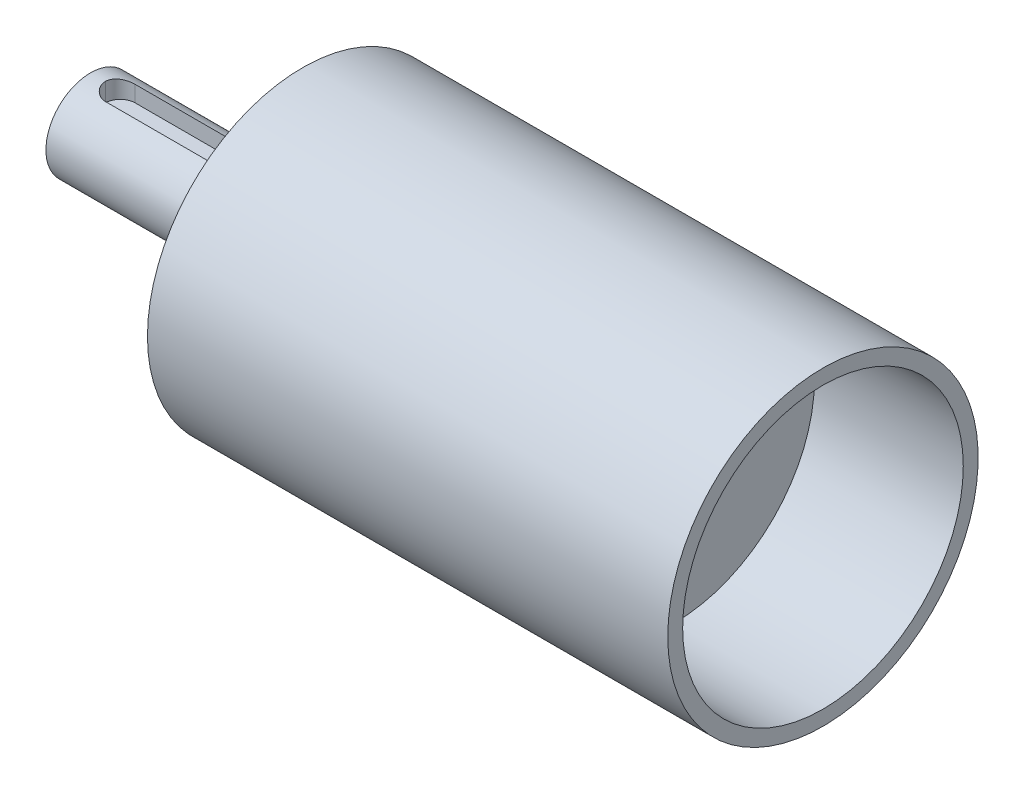
SolidWorks part; units mm, degrees
ref_plane "Front Plane" through (0, 0, 0) normal (0, 0, 1) x (1, 0, 0)
ref_plane "Top Plane" through (0, 0, 0) normal (0, 1, 0) x (1, 0, 0)
ref_plane "Right Plane" through (0, 0, 0) normal (1, 0, 0) x (0, 0, -1)
sketch "Sketch1" plane through (0, 0, 0) normal (1, 0, 0) x (0, 0, -1)
  circle A0 centre (0, 0) radius 5.99
  dimension "D1" = 11.98
extrude "Extrude1" add sketch "Sketch1" along normal blind 25.9
sketch "Sketch2" plane through (25.9, 0, 0) normal (1, 0, 0) x (0, 0, -1)
  circle A0 centre (0, 0) radius 13.985
  dimension "D1" = 27.97
extrude "Extrude2" add sketch "Sketch2" along normal blind 2.6
sketch "Sketch3" plane through (28.5, 0, 0) normal (1, 0, 0) x (0, 0, -1)
  circle A0 centre (0, 0) radius 20.85
  dimension "D1" = 41.7
extrude "Extrude3" add sketch "Sketch3" along normal blind 69.9
sketch "Sketch6" plane through (0, 0, 0) normal (-1, 0, 0) x (0, 0, 1)
  line L0 (0, 5.99) -> (0, 3.49)
  line L1 (-2, 3.49) -> (2, 3.49)
  line L2 (2, 3.49) -> (2, 5.99)
  line L3 (2, 5.99) -> (-2, 5.99)
  line L4 (-2, 5.99) -> (-2, 3.49)
  circle A0 centre (0, 0) radius 5.99 construction
  circle M1 centre (0, 0) radius 5.99
  dimension "D1" = 2.5
  dimension "D2" = 4
extrude "Cut-Extrude1" cut sketch "Sketch6" against normal blind 20 from offset 2 contours L4 L1 L0 M1 | L1 L2 L0 M1 offset against normal yes
fillet "Fillet8" radius 2 4 edges at (2, 4.5681, -2) (22, 4.5681, -2) (2, 4.5681, 2) (22, 4.5681, 2)
sketch "Sketch7" plane through (28.5, 0, 0) normal (-1, 0, 0) x (0, 0, 1)
  circle A1 centre (0, 17.5) radius 2
  circle A2 centre (17.5, 0) radius 2
  circle A3 centre (0, -17.5) radius 2
  circle A4 centre (-17.5, 0) radius 2
  dimension "D2" = 4
extrude "Cut-Extrude2" cut sketch "Sketch7" against normal blind 8
sketch "Sketch9" plane through (98.4, 0, 0) normal (1, 0, 0) x (0, 0, -1)
  circle A1 centre (0, 0) radius 18.85
extrude "Cut-Extrude3" cut sketch "Sketch9" against normal blind 20
